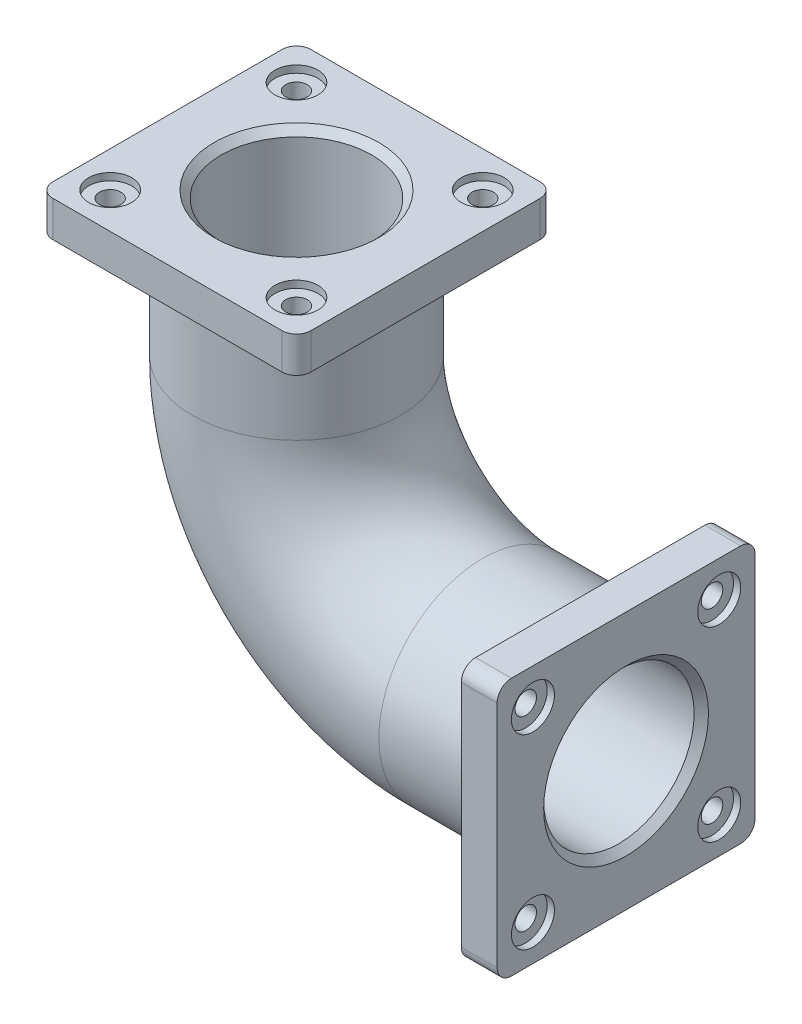
SolidWorks part; units mm, degrees
ref_plane "Front Plane" through (0, 0, 0) normal (0, 0, 1) x (1, 0, 0)
ref_plane "Top Plane" through (0, 0, 0) normal (0, 1, 0) x (1, 0, 0)
ref_plane "Right Plane" through (0, 0, 0) normal (1, 0, 0) x (0, 0, -1)
sketch "Sketch1" plane through (0, 0, 0) normal (0, 0, 1) x (1, 0, 0)
  line L0 (0, 260) -> (0, 410)
  line L1 (260, 0) -> (410, 0)
  arc A0 (260, 0) -> (0, 260) centre (260, 260) cw
  point P6 (0, 0)
  dimension "D3" = 260
  dimension "D1" = 410
  dimension "D2" = 410
sweep "Sweep-Thin1" add path "Sketch1" circular profile diameter 290 parameters "D1"=40, "D3"=290
sketch "Sketch24" plane through (410, 0, 0) normal (1, 0, 0) x (0, 0, -1)
  line L1 (-160, 180) -> (160, 180)
  line L2 (-180, 160) -> (-180, -160)
  line L3 (-160, -180) -> (160, -180)
  line L4 (180, 160) -> (180, -160)
  line L5 (-180, 180) -> (180, -180) construction
  line L6 (-180, -180) -> (180, 180) construction
  arc A0 (-160, 180) -> (-180, 160) centre (-160, 160) ccw
  arc A1 (160, -180) -> (180, -160) centre (160, -160) ccw
  arc A2 (-160, -180) -> (-180, -160) centre (-160, -160) cw
  arc A3 (180, 160) -> (160, 180) centre (160, 160) ccw
  point P0 (0, 0)
  dimension "D3" = 20
  dimension "D4" = 20
  dimension "D1" = 360
  dimension "D2" = 360
extrude "Boss-Extrude2" add sketch "Sketch24" along normal blind 50
sketch "Sketch26" plane through (460, 0, 0) normal (1, 0, 0) x (0, 0, -1)
  line L0 (-180, 160) -> (-180, -160) construction
  line L1 (-160, -180) -> (160, -180) construction
  circle A0 centre (-130, -130) radius 30
  circle A1 centre (-130, -130) radius 15
  circle A2 centre (2470, -130) radius 15
  circle A3 centre (2470, -130) radius 30
  circle A4 centre (2470, 130) radius 15
  circle A5 centre (2470, 130) radius 30
  circle A6 centre (-130, 130) radius 15
  circle A7 centre (-130, 130) radius 30
  circle A8 centre (130, 130) radius 30
  circle A9 centre (130, 130) radius 15
  circle A10 centre (130, -130) radius 30
  circle A11 centre (130, -130) radius 15
  circle A12 centre (-130, -130) radius 30
  circle A13 centre (-130, -130) radius 15
  circle A14 centre (0, 0) radius 95.7683
  point P28 (0, 0)
  dimension "D1" = 60
  dimension "D4" = 2
  dimension "D2" = 50
  dimension "D3" = 50
  dimension "D5" = 2
  dimension "D6" = 2
  dimension "D7" = 2
extrude "Cut-Extrude2" cut sketch "Sketch26" against normal blind 10 contours A7 A6 | A0 A1 | A8 A9 | A10 A11 region at (460, -130, 159.1515) region at (460, 130, 159.1515) region at (460, 130, -100.8485) region at (460, -130, -100.8485)
extrude "Cut-Extrude3" cut sketch "Sketch26<3>" against normal blind 50 contours A6 | A1 | A11 | A9 region at (460, -130, 130) region at (460, 130, 130) region at (460, 130, -130) region at (460, -130, -130)
sketch "Sketch26<3>" plane through (460, 0, 0) normal (1, 0, 0) x (0, 0, -1) same geometry as "Sketch26"
sketch "Sketch27" plane through (0, 410, 0) normal (0, 1, 0) x (1, 0, 0)
  line L1 (-160, 180) -> (160, 180)
  line L2 (-180, 160) -> (-180, -160)
  line L3 (-160, -180) -> (160, -180)
  line L4 (180, 160) -> (180, -160)
  line L5 (-180, 180) -> (180, -180) construction
  line L6 (-180, -180) -> (180, 180) construction
  arc A0 (-180, -160) -> (-160, -180) centre (-160, -160) ccw
  arc A1 (160, -180) -> (180, -160) centre (160, -160) ccw
  arc A2 (180, 160) -> (160, 180) centre (160, 160) ccw
  arc A3 (-160, 180) -> (-180, 160) centre (-160, 160) ccw
  point P0 (0, 0)
  dimension "D3" = 20
  dimension "D1" = 360
  dimension "D2" = 360
extrude "Boss-Extrude3" add sketch "Sketch27" along normal blind 50
sketch "Sketch28" plane through (0, 460, 0) normal (0, 1, 0) x (1, 0, 0)
  line L0 (-180, 160) -> (-180, -160) construction
  line L1 (-160, -180) -> (160, -180) construction
  circle A0 centre (-130, -130) radius 30
  circle A1 centre (-130, -130) radius 15
  circle A2 centre (130, -130) radius 30
  circle A3 centre (130, -130) radius 15
  circle A4 centre (130, 130) radius 30
  circle A5 centre (130, 130) radius 15
  circle A6 centre (-130, 130) radius 30
  circle A7 centre (-130, 130) radius 15
  dimension "D1" = 50
  dimension "D2" = 50
  dimension "D3" = 2
  dimension "D4" = 2
extrude "Cut-Extrude4" cut sketch "Sketch28" against normal blind 10 contours A6 A7 | A0 A1 | A2 A3 | A4 A5 region at (-159.1515, 460, 130) region at (100.8485, 460, 130) region at (100.8485, 460, -130) region at (-159.1515, 460, -130)
extrude "Cut-Extrude5" cut sketch "Sketch28<3>" against normal blind 50 contours A7 | A1 | A5 | A3 region at (-130, 460, 130) region at (130, 460, 130) region at (130, 460, -130) region at (-130, 460, -130)
sketch "Sketch28<3>" plane through (0, 460, 0) normal (0, 1, 0) x (1, 0, 0) same geometry as "Sketch28"
sketch "Sketch29" plane through (460, 0, 0) normal (1, 0, 0) x (0, 0, -1)
  circle A0 centre (0, 0) radius 105
  dimension "D1" = 210
chamfer "Chamfer1" distance 10 angle 45 1 edges at (410, 0, 105)
extrude "Cut-Extrude7" cut sketch "Sketch29" against normal blind 75 contours A0
sketch "Sketch30" plane through (0, 460, 0) normal (0, 1, 0) x (1, 0, 0)
  circle A0 centre (0, 0) radius 105
  point P3 (-72.5282, 144.4471)
extrude "Cut-Extrude8" cut sketch "Sketch30" against normal blind 75 contours A0 region at (0, 460, 0)
chamfer "Chamfer2" distance 10 angle 45 1 edges at (0, 460, 105)
chamfer "Chamfer3" distance 10 angle 45 1 edges at (460, 0, -105)
